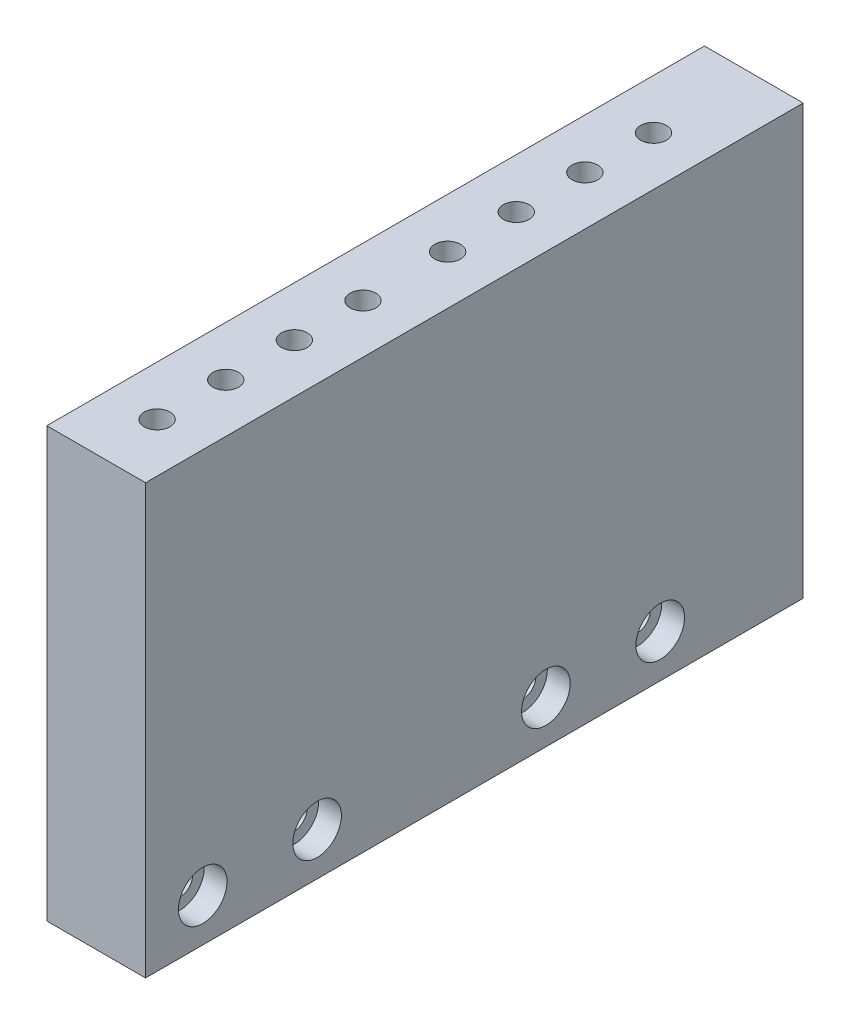
SolidWorks part; units mm, degrees
ref_plane "Front Plane" through (0, 0, 0) normal (0, 0, 1) x (1, 0, 0)
ref_plane "Top Plane" through (0, 0, 0) normal (0, 1, 0) x (1, 0, 0)
ref_plane "Right Plane" through (0, 0, 0) normal (1, 0, 0) x (0, 0, -1)
sketch "Sketch1" plane through (0, 0, 0) normal (1, 0, 0) x (0, 0, -1)
  line L1 (-57.5, -37.5) -> (57.5, -37.5)
  line L2 (-57.5, -37.5) -> (-57.5, 37.5)
  line L3 (-57.5, 37.5) -> (57.5, 37.5)
  line L4 (57.5, -37.5) -> (57.5, 37.5)
  line L5 (-57.5, -37.5) -> (57.5, 37.5) construction
  line L6 (-57.5, 37.5) -> (57.5, -37.5) construction
  point P0 (0, 0)
  dimension "D1" = 115
  dimension "D2" = 75
extrude "Boss-Extrude1" add sketch "Sketch1" along normal blind 17.272
hole_wizard "M4 Clearance Hole1" positions "Sketch2" profile "Sketch4" hole size "M4" standard "ANSI Metric"
sketch "Sketch2" plane through (0, 37.5, 0) normal (0, 1, 0) x (1, 0, 0)
  line L0 (8.692, -22.9) -> (8.692, 27.9)
  line L3 (17.272, -57.5) -> (0, -57.5) construction
  line L5 (17.272, 57.5) -> (17.272, -57.5) construction
  point P1 (8.692, -22.9)
  point P2 (8.692, 27.9)
  point P7 (8.692, 2.5)
  dimension "D1" = 50.8
  dimension "D2" = 8.58
  dimension "D3" = 60
sketch "Sketch4" plane through (8.692, 37.5, 22.9) normal (1, 0, 0) x (0, 0, 1)
  line L0 (0, 0) -> (0, 7.3519)
  line L1 (0, 7.3519) -> (2.25, 6)
  line L2 (2.25, 6) -> (2.25, 0)
  line L5 (2.25, 0) -> (0, 0)
  line L10 (0, 7.3519) -> (-2.25, 6) construction
  line L11 (0, -6.35) -> (0, 107.95) construction
  dimension "Hole Dia." = 4.5
  dimension "Hole Depth" = 6
  dimension "Drill Angle" = 118
sketch "Sketch5" plane through (0, 0, 0) normal (-1, 0, 0) x (0, 0, 1)
  line L0 (25.15, 37.5) -> (20.65, 37.5) construction
  line L1 (-25.65, 37.5) -> (-30.15, 37.5) construction
  line L2 (25.15, 37.5) -> (20.65, 37.5)
  line L3 (-25.65, 37.5) -> (-30.15, 37.5)
  line L4 (-57.5, 37.5) -> (57.5, 37.5) construction
  line L5 (-33.15, 26.5) -> (-22.65, 26.5)
  line L6 (-33.15, 26.5) -> (-33.15, 31.5)
  line L7 (-33.15, 31.5) -> (-22.65, 31.5)
  line L8 (-22.65, 26.5) -> (-22.65, 31.5)
  line L9 (-33.15, 26.5) -> (-22.65, 31.5) construction
  line L10 (-33.15, 31.5) -> (-22.65, 26.5) construction
  line L11 (17.65, 26.5) -> (28.15, 26.5)
  line L12 (17.65, 26.5) -> (17.65, 31.5)
  line L13 (17.65, 31.5) -> (28.15, 31.5)
  line L14 (28.15, 26.5) -> (28.15, 31.5)
  line L15 (17.65, 26.5) -> (28.15, 31.5) construction
  line L16 (17.65, 31.5) -> (28.15, 26.5) construction
  point P4 (-27.9, 29)
  point P11 (22.9, 29)
  point P12 (-27.9, 37.5)
  dimension "D1" = 5
  dimension "D2" = 6
  dimension "D3" = 10.5
  dimension "D4" = 2
extrude "Cut-Extrude1" cut sketch "Sketch5" against normal blind 14.08 contours L5 L8 L7 L6 | L11 L14 L13 L12 region at (0, 29, -27.9) region at (0, 29, 22.9)
pattern_linear "LPattern1" count 2 spacing 12 along (0, 0, -1) count 3 spacing 12 along (0, 0, 1) of "M4 Clearance Hole1", "Cut-Extrude1"
hole_wizard "CBORE for M5 Hex Head Bolt1" positions "Sketch6" profile "Sketch8" counterbore size "M5" standard "ANSI Metric" end condition through all
sketch "Sketch6" plane through (17.272, 0, 0) normal (1, 0, 0) x (0, 0, -1)
  line L0 (-27.5, -30) -> (12.5, -30)
  line L1 (-57.5, -37.5) -> (57.5, -37.5) construction
  line L2 (-47.5, -30) -> (32.5, -30)
  point P2 (12.5, -30)
  point P7 (-27.5, -30)
  point P13 (-7.5, -30)
  point P16 (-47.5, -30)
  point P17 (32.5, -30)
  point P25 (-7.5, -30)
  dimension "D1" = 40
  dimension "D2" = 7.5
  dimension "D3" = 50
  dimension "D4" = 80
sketch "Sketch8" plane through (17.272, -30, -32.5) normal (0, 1, 0) x (0, 0, -1)
  line L0 (0, 0) -> (0, 17.272)
  line L1 (0, 17.272) -> (2.25, 17.272)
  line L3 (2.25, 17.272) -> (2.25, 4)
  line L4 (2.25, 4) -> (4.25, 4)
  line L5 (4.25, 4) -> (4.25, 0)
  line L7 (4.25, 0) -> (0, 0)
  line L11 (0, -6.35) -> (0, 107.95) construction
  dimension "Thru Hole Dia." = 4.5
  dimension "Thru Hole Depth" = 17.272
  dimension "C'Bore Dia." = 8.5
  dimension "C'Bore Depth" = 4
sketch "Sketch12" plane through (0, 0, 0) normal (-1, 0, 0) x (0, 0, 1)
  line L0 (57.5, 37.5) -> (57.5, -37.5) construction
  line L1 (-12.5, -22.1) -> (27.5, -22.1)
  line L2 (-12.5, -22.1) -> (-12.5, 21.5)
  line L3 (-12.5, 21.5) -> (27.5, 21.5)
  line L4 (27.5, -22.1) -> (27.5, 21.5)
  line L5 (-12.5, -22.1) -> (27.5, 21.5) construction
  line L6 (-12.5, 21.5) -> (27.5, -22.1) construction
  line L7 (57.5, -37.5) -> (-57.5, -37.5) construction
  line L9 (-2.5, -17.1) -> (17.5, -17.1)
  line L10 (-2.5, -17.1) -> (-2.5, 21.5)
  line L11 (-2.5, 21.5) -> (17.5, 21.5)
  line L12 (17.5, -17.1) -> (17.5, 21.5)
  line L13 (-2.5, -17.1) -> (17.5, 21.5) construction
  line L14 (-2.5, 21.5) -> (17.5, -17.1) construction
  point P0 (7.5, -0.3)
  point P10 (7.5, 2.2)
  point P15 (0, 0)
  dimension "D1" = 50
  dimension "D2" = 15.4
  dimension "D3" = 5
  dimension "D4" = 40
  dimension "D5" = 10
  dimension "D6" = 5
  dimension "D7" = 38.6
extrude "Boss-Extrude3" add sketch "Sketch12" along normal blind 17.228 contours L12 L9 L10 L3 L2 L1 L4 region at (0, -0.3, -11.9083)
chamfer "Chamfer2" distance 38.6 distance2 17.228 2 edges at (-17.228, 21.5, -7.5) (-17.228, 21.5, 22.5) first distance on face at (-17.228, 0.95, 7.5)
hole_wizard "M4 Clearance Hole3" positions "Sketch13" profile "Sketch15" hole size "M4" standard "ANSI Metric" end condition through all
sketch "Sketch13" plane through (0, -17.1, 0) normal (0, 1, 0) x (1, 0, 0)
  line L0 (-17.228, -17.5) -> (0, 2.5)
  point P6 (-8.614, -7.5)
  point P10 (0, 0)
sketch "Sketch15" plane through (-8.614, -17.1, 7.5) normal (1, 0, 0) x (0, 0, 1)
  line L0 (0, 0) -> (0, 20.4)
  line L1 (0, 20.4) -> (2.25, 20.4)
  line L2 (2.25, 20.4) -> (2.25, 0)
  line L5 (2.25, 0) -> (0, 0)
  line L11 (0, -6.35) -> (0, 107.95) construction
  dimension "Thru Hole Dia." = 4.5
  dimension "Thru Hole Depth" = 20.4
